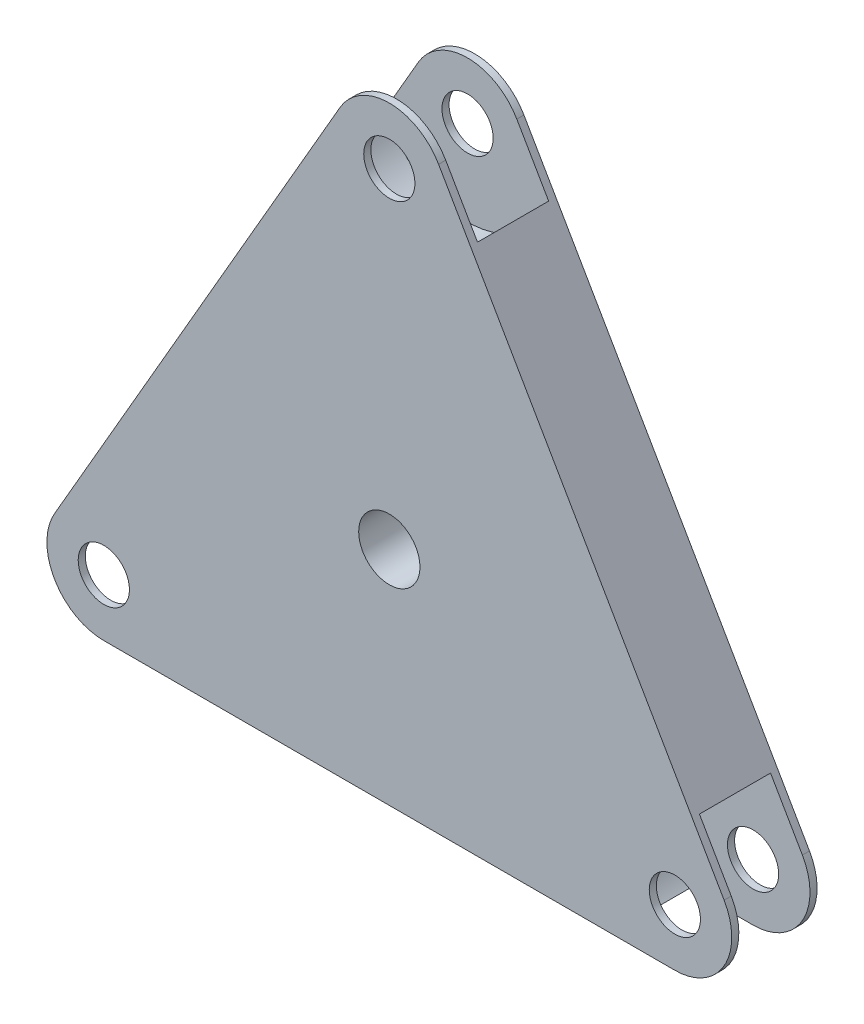
SolidWorks part; units mm, degrees
ref_plane "Plan de face" through (0, 0, 0) normal (0, 0, 1) x (1, 0, 0)
ref_plane "Plan de dessus" through (0, 0, 0) normal (0, 1, 0) x (1, 0, 0)
ref_plane "Plan de droite" through (0, 0, 0) normal (1, 0, 0) x (0, 0, -1)
sketch "Esquisse1" plane through (0, 0, 0) normal (0, 0, 1) x (1, 0, 0)
  line L1 (-8.6603, 62.9423) -> (-58.8397, -23.9711)
  line L2 (-50.1795, -38.9711) -> (50.1795, -38.9711)
  line L3 (58.8397, -23.9711) -> (8.6603, 62.9423)
  circle A0 centre (0, 0) radius 38.9711 construction
  arc A1 (50.1795, -38.9711) -> (58.8397, -23.9711) centre (50.1795, -28.9711) ccw
  arc A2 (-58.8397, -23.9711) -> (-50.1795, -38.9711) centre (-50.1795, -28.9711) ccw
  arc A3 (-8.6603, 62.9423) -> (8.6603, 62.9423) centre (0, 57.9423) cw
  point P8 (67.5, -38.9711)
  point P13 (0, 77.9423)
  dimension "D2" = 10
  dimension "D1" = 135
extrude "Boss.-Extru.1" add sketch "Esquisse1" along normal blind 15
sketch "Esquisse2" plane through (0, 0, 0) normal (0, 0, 1) x (1, 0, 0)
  circle A0 centre (0, 57.9423) radius 15
  arc A1 (8.6603, 62.9423) -> (-8.6603, 62.9423) centre (0, 57.9423) ccw construction
extrude "Enlèv. mat.-Extru.1" cut sketch "Esquisse2" against normal mid plane 12.5 from offset 7.5
sketch "Esquisse3" plane through (0, 0, 0) normal (0, 1, 0) x (1, 0, 0)
  line L0 (0, 0.5506) -> (0, 12.8411) construction
pattern_circular "Répétition circulaire1" count 3 over 360 about axis through (0, 0, -0.5506) along (0, 0, -1) of "Enlèv. mat.-Extru.1"
sketch "Esquisse6" plane through (0, 0, 0) normal (0, 0, -1) x (-1, 0, 0)
  arc A0 (8.6603, 62.9423) -> (-8.6603, 62.9423) centre (0, 57.9423) ccw construction
  arc A1 (-58.8397, -23.9711) -> (-50.1795, -38.9711) centre (-50.1795, -28.9711) ccw construction
  arc A2 (50.1795, -38.9711) -> (58.8397, -23.9711) centre (50.1795, -28.9711) ccw construction
  point P0 (0, 57.9423)
  point P2 (50.1795, -28.9711)
  point P5 (-50.1795, -28.9711)
hole_wizard "Dégagement M81" positions "Esquisse6" profile "Esquisse5" hole size "M8" standard "ISO" end condition through all
sketch "Esquisse5" plane through (0, 57.9423, 0) normal (1, 0, 0) x (0, 1, 0)
  line L0 (0, 0) -> (0, 15)
  line L1 (0, 15) -> (4.5, 15)
  line L2 (4.5, 15) -> (4.5, 0)
  line L5 (4.5, 0) -> (0, 0)
  line L11 (0, -6.35) -> (0, 107.95) construction
  dimension "Diamètre du perçage jusqu'au prochain" = 9
  dimension "Profondeur du perçage jusqu'au prochain" = 15
sketch "Esquisse7" plane through (0, 0, 0) normal (0, 0, -1) x (-1, 0, 0)
  circle A0 centre (0, 0) radius 5.3832
  circle A1 centre (0, 0) radius 7.4602
extrude "Boss.-Extru.2" add sketch "Esquisse7" along normal blind 12.5
extrude "Enlèv. mat.-Extru.2" cut sketch "Esquisse7<3>" against normal through all contours A0
sketch "Esquisse7<3>" plane through (0, 0, 0) normal (0, 0, -1) x (-1, 0, 0) same geometry as "Esquisse7"
hole_wizard "Dégagement M31" positions "Esquisse3D2" profile "Esquisse9" hole size "M3" standard "ISO" end condition through all
sketch3d "Esquisse3D2"
  point P0 (3.3854, 6.6478, -6.6959)
  point P3 (0, 0, 0)
sketch "Esquisse9" plane through (3.3854, 6.6478, -6.6959) normal (0, 0, 1) x (-0.8911, 0.4538, 0)
  line L0 (0, 0) -> (0, 69.4967)
  line L1 (0, 69.4967) -> (1.7, 69.4967)
  line L2 (1.7, 69.4967) -> (1.7, 0)
  line L5 (1.7, 0) -> (0, 0)
  line L11 (0, -6.35) -> (0, 107.95) construction
  dimension "Diamètre du perçage jusqu'au prochain" = 3.4
  dimension "Profondeur du perçage jusqu'au prochain" = 69.4967
equation "\"D1@Esquisse1\"=135"
